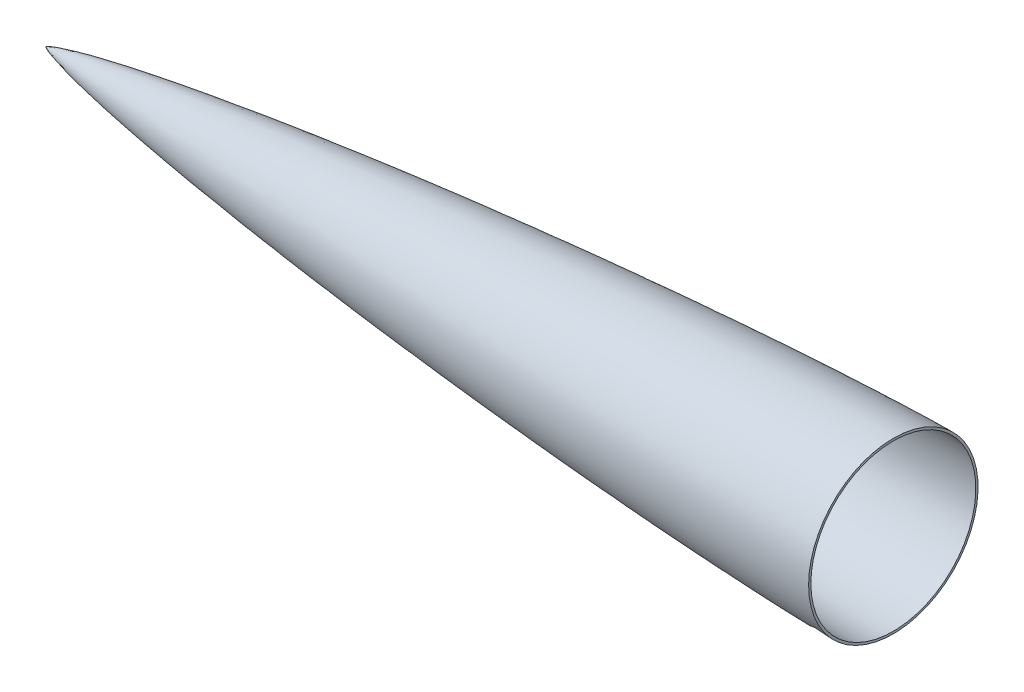
SolidWorks part; units mm, degrees
material "Fibra di Carbonio"
ref_plane "Front Plane" through (0, 0, 0) normal (0, 0, 1) x (1, 0, 0)
ref_plane "Top Plane" through (0, 0, 0) normal (0, 1, 0) x (1, 0, 0)
ref_plane "Right Plane" through (0, 0, 0) normal (1, 0, 0) x (0, 0, -1)
sketch "Sketch2" plane through (0, 0, 0) normal (0, 0, 1) x (1, 0, 0)
  line L0 (0, 0) -> (750, 0) construction
  line L1 (750, 75) -> (750, 0) construction
  line L2 (0, 0) -> (4.5526, 0)
  line L3 (750, 75) -> (750.005, 73)
  line L4 (4.5526, 0) -> (18.241, -6.6941) construction
  line L5 (0, 0) -> (17.3624, -8.4908) construction
  spline S0 degree 4 poles (0, 0) (0.0027, 0.0074) (0.0091, 0.0215) (0.0269, 0.047) (0.0684, 0.0933) (0.1314, 0.151) (0.2168, 0.2183) (0.3382, 0.3041) (0.4839, 0.3974) (0.6551, 0.4981) (0.8516, 0.6056) (1.1377, 0.7534) (1.5815, 0.9661) (2.3351, 1.2961) (3.6829, 1.8266) (6.1115, 2.6745) (10.5746, 4.038) (18.9517, 6.252) (33.5701, 9.5653) (58.4067, 14.4079) (92.5079, 20.1209) (133.842, 26.2251) (179.8092, 32.3065) (225.8421, 37.8632) (271.9254, 42.9839) (318.0491, 47.7253) (364.2071, 52.1207) (410.3947, 56.191) (456.6091, 59.9459) (502.848, 63.3865) (549.1098, 66.5042) (595.3934, 69.2798) (635.9102, 71.3773) (670.652, 72.8985) (698.6683, 73.9066) (717.5285, 74.458) (733.0226, 74.8041) (742.7236, 74.948) (747.5745, 74.994) (750, 75) knots 0 0 0 0 0 0.000041 0.000082 0.000164 0.000329 0.000493 0.000658 0.000951 0.001245 0.001545 0.001844 0.002657 0.003853 0.005902 0.009516 0.016281 0.028569 0.051794 0.088907 0.150314 0.211721 0.273128 0.334535 0.395942 0.457348 0.518755 0.580162 0.641569 0.702976 0.764383 0.825789 0.887196 0.9179 0.948603 0.974302 0.987151 1 1 1 1 1 construction
  spline S1 degree 4 poles (0, 0) (0.0027, 0.0074) (0.0091, 0.0215) (0.0269, 0.047) (0.0684, 0.0933) (0.1314, 0.151) (0.2168, 0.2183) (0.3382, 0.3041) (0.4839, 0.3974) (0.6551, 0.4981) (0.8516, 0.6056) (1.1377, 0.7534) (1.5815, 0.9661) (2.3351, 1.2961) (3.6829, 1.8266) (6.1115, 2.6745) (10.5746, 4.038) (18.9517, 6.252) (33.5701, 9.5653) (58.4067, 14.4079) (92.5079, 20.1209) (133.842, 26.2251) (179.8092, 32.3065) (225.8421, 37.8632) (271.9254, 42.9839) (318.0491, 47.7253) (364.2071, 52.1207) (410.3947, 56.191) (456.6091, 59.9459) (502.848, 63.3865) (549.1098, 66.5042) (595.3934, 69.2798) (635.9102, 71.3773) (670.652, 72.8985) (698.6683, 73.9066) (717.5285, 74.458) (733.0226, 74.8041) (742.7236, 74.948) (747.5745, 74.994) (750, 75) knots 0 0 0 0 0 0.000041 0.000082 0.000164 0.000329 0.000493 0.000658 0.000951 0.001245 0.001545 0.001844 0.002657 0.003853 0.005902 0.009516 0.016281 0.028569 0.051794 0.088907 0.150314 0.211721 0.273128 0.334535 0.395942 0.457348 0.518755 0.580162 0.641569 0.702976 0.764383 0.825789 0.887196 0.9179 0.948603 0.974302 0.987151 1 1 1 1 1
  spline S2 degree 1 poles (4.5526, 0) (750.005, 73) knots 0 0 1 1 construction
  spline S3 degree 3 poles (4.5526, 0) (5.445, 0.3249) (7.239, 0.923) (10.9289, 2.0351) (17.4708, 3.796) (26.9445, 6.0175) (38.3871, 8.4241) (53.7067, 11.3983) (72.9318, 14.7925) (96.0679, 18.5265) (119.2498, 22.0067) (150.2024, 26.3764) (188.9573, 31.415) (235.5315, 36.9454) (282.158, 42.0423) (328.826, 46.7595) (391.0967, 52.5838) (469.0103, 59.0427) (547.0044, 64.4339) (609.4413, 68.0319) (656.2876, 70.325) (695.3421, 71.8297) (722.6802, 72.5863) (738.3058, 72.8883) (746.1038, 72.9903) (750.005, 73) knots 0.005737 0.005737 0.005737 0.005737 0.00962 0.013504 0.021272 0.036807 0.052343 0.067878 0.098949 0.130019 0.16109 0.192161 0.254302 0.316444 0.378585 0.440727 0.502868 0.627151 0.751434 0.813576 0.875717 0.937859 0.968929 0.984465 1 1 1 1
  dimension "D1" = 75
  dimension "D2" = 750
  dimension "D3" = 2
revolve "Revolve1" add sketch "Sketch2" angle 360 about L0
